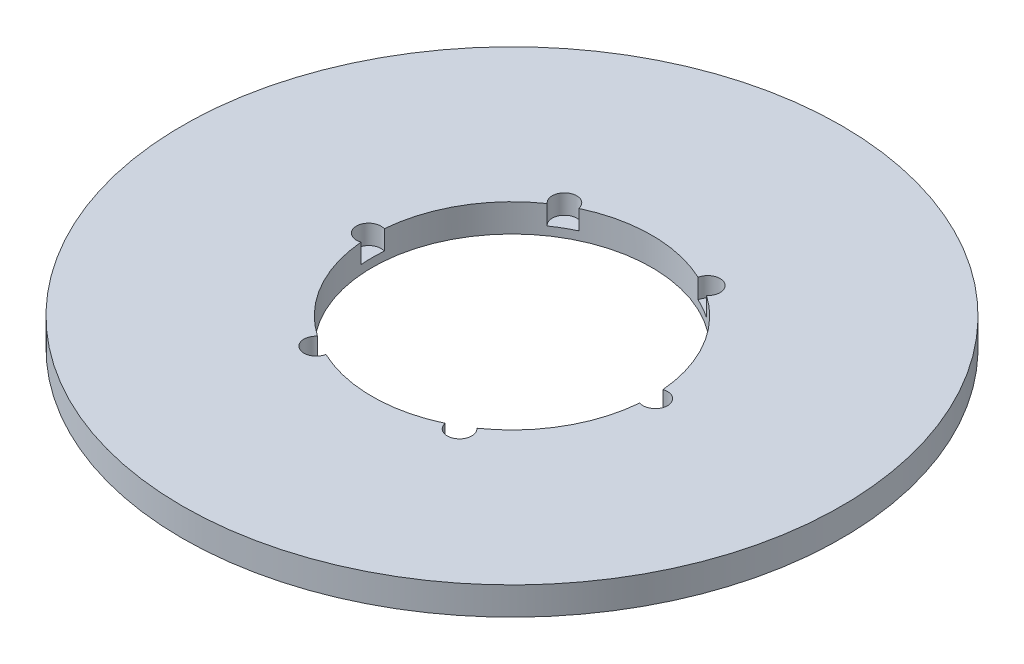
SolidWorks part; units mm, degrees
ref_plane "Front Plane" through (0, 0, 0) normal (0, 0, 1) x (1, 0, 0)
ref_plane "Top Plane" through (0, 0, 0) normal (0, 1, 0) x (1, 0, 0)
ref_plane "Right Plane" through (0, 0, 0) normal (1, 0, 0) x (0, 0, -1)
sketch "Sketch1" plane through (0, 0, 0) normal (0, 1, 0) x (1, 0, 0)
  circle A0 centre (0, 0) radius 82.5
  dimension "FLANGE_OD" = 165
extrude "Boss-Extrude1" add sketch "Sketch1" along normal blind 7
sketch "Sketch2" plane through (0, 0, 0) normal (0, 1, 0) x (1, 0, 0)
  circle A0 centre (0, 0) radius 35
  dimension "BORE_D" = 70
extrude "Cut-Extrude1" cut sketch "Sketch2" along normal through all
sketch "Sketch3" plane through (0, 7, 0) normal (0, 1, 0) x (1, 0, 0)
  circle A0 centre (0, 0) radius 35.8785 construction
  circle A1 centre (-35.8785, 0) radius 3.067
  dimension "BOLT_D" = 6.1339
  dimension "BOLT_PCD" = 71.7571
extrude "Cut-Extrude2" cut sketch "Sketch3" against normal blind 4.8652
pattern_circular "CirPattern1" count 6 over 360 about axis through (0, 0, 0) along (0, 1, 0) of "Cut-Extrude2"
